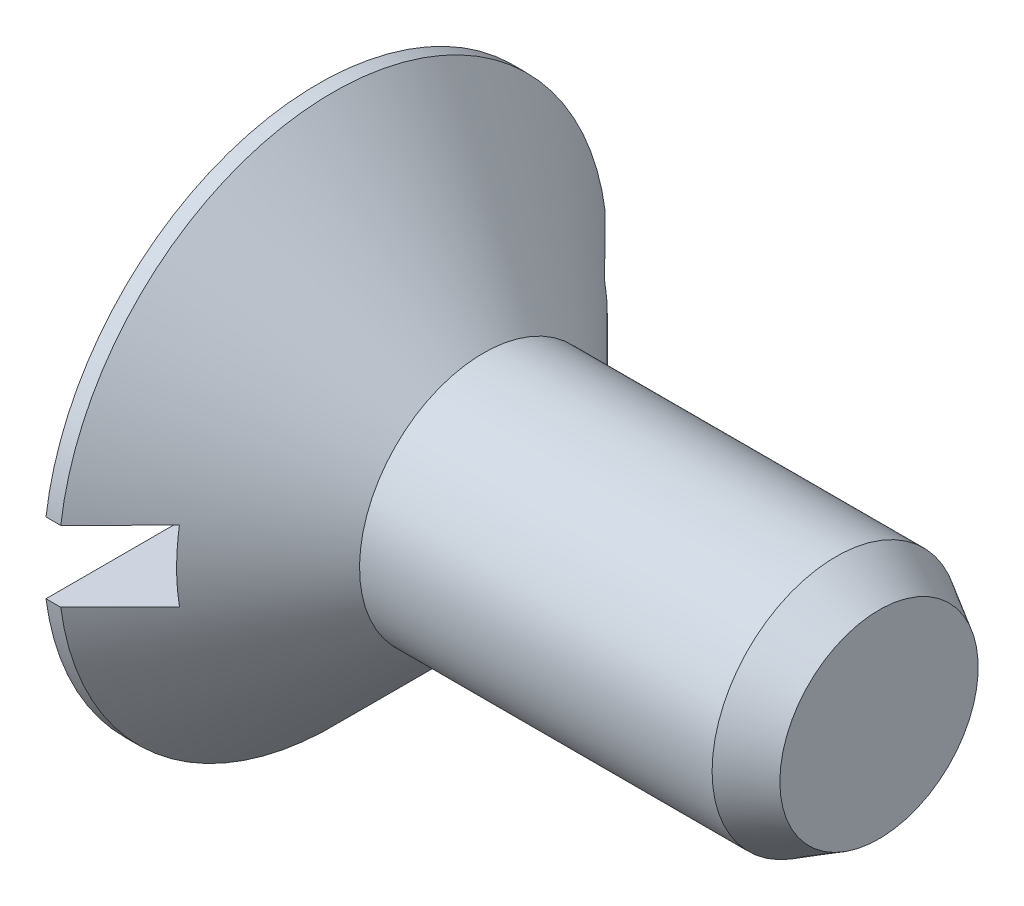
SolidWorks part; units mm, degrees
ref_plane "Front" through (0, 0, 0) normal (0, 0, 1) x (1, 0, 0)
ref_plane "Top" through (0, 0, 0) normal (0, 1, 0) x (1, 0, 0)
ref_plane "Right" through (0, 0, 0) normal (1, 0, 0) x (0, 0, -1)
sketch "Sketch1" plane through (0, 0, 0) normal (0, 0, 1) x (1, 0, 0)
  line L0 (0, 4.65) -> (0.25, 4.65)
  line L1 (0.25, 4.65) -> (2.8, 2.1)
  line L2 (2.8, 2.1) -> (9.5, 2.1)
  line L3 (9.5, 2.1) -> (9.5, 0)
  line L4 (9.5, 0) -> (0, 0)
  line L5 (0, 0) -> (0, 4.65)
  line L6 (6.6207, 0) -> (-0.9387, 0) construction
  dimension "D1" = 45
  dimension "k" = 2.8
revolve "Revolve1" add sketch "Sketch1" angle 360 about L6
cosmetic thread "ThreadCosmetic" [suppressed] parameters "D2"=3.8
sketch "Sketch2" plane through (0, 0, 0) normal (0, 0, 1) x (1, 0, 0)
  line L0 (0, 4.65) -> (0, -4.65) construction
  line L1 (0, 0.6) -> (1.25, 0.6)
  line L2 (0, 0.6) -> (0, -0.6)
  line L3 (0, -0.6) -> (1.25, -0.6)
  line L4 (1.25, 0.6) -> (1.25, -0.6)
  dimension "n" = 1.2
  dimension "t" = 1.25
extrude "Cut-Extrude1" cut sketch "Sketch2" against normal through all and the other way through all
chamfer "Chamfer1" distance 0.42 angle 60 1 edges at (9.5, 0, -2.1) first distance on face at (9.5, 0, -2.1)
sketch "Sketch4" plane through (0, 0, 0) normal (0, 0, 1) x (1, 0, 0)
  line L0 (3.2136, 1.9) -> (2.9636, 1.9)
  line L1 (2.9636, 1.9) -> (2.8481, 2.1)
  line L2 (3.2136, 1.9) -> (3.329, 2.1)
  line L3 (2.8481, 2.1) -> (2.8481, 2.35)
  line L4 (3.329, 2.1) -> (3.329, 2.35)
  line L5 (2.8481, 2.35) -> (3.329, 2.35)
  line L6 (3.0886, 1.9) -> (3.0886, 0) construction
  line L7 (0, 0) -> (7.3035, 0) construction
  line L9 (8.7725, 2.1) -> (2.8, 2.1) construction
  line L12 (2.8, 2.1) -> (2.8, -2.1) construction
  dimension "D2" = 60
  dimension "D3" = 0.25
  dimension "minordia" = 3.8
  dimension "threadstart" = 0.2886
revolve "ThreadSchematic" [suppressed] cut sketch "Sketch4" angle 360 about L7
pattern_linear "ThdSchPat" [suppressed] count 14 spacing 0.4809 along (1, 0, 0) of bodies 137
sketch "Sketch3" plane through (0, 0, 0) normal (0, 0, 1) x (1, 0, 0)
  line L0 (2.8, 2.1) -> (9.5, 2.1) construction
  line L2 (7.5, 2.1) -> (8, 2.1) construction
  line L3 (9.5, 2.1) -> (9.5, 0) construction
  line L4 (8, 2.1) -> (9.5, 0)
  line L5 (2.9, 0) -> (5.4301, 0) construction
  line L6 (9.5, 0) -> (9.7, 0)
  line L7 (9.7, 0) -> (9.7, 2.1)
  line L8 (9.7, 2.1) -> (9.5, 2.1)
  line L9 (8, 2.1) -> (9.5, 2.1)
  dimension "D1" = 0.5
revolve "EndCone" [suppressed] cut sketch "Sketch3" angle 360 about L5
equation "\"minordia@Sketch4\" = \"D2@ThreadCosmetic\""
equation "\"D1@Chamfer1\" = \"d@Sketch1\" / 10"
equation "\"D1@Sketch3\" = \"y@Sketch3\" / 4"
equation "\"threadstart@Sketch4\" = \"advance@Sketch4\"*0.6"
equation "\"D1@ThdSchPat\" = int(((\"l@Sketch1\"-\"k@Sketch1\")/\"advance@Sketch4\") + 0.999)"
equation "\"D3@ThdSchPat\" =\"advance@Sketch4\""
